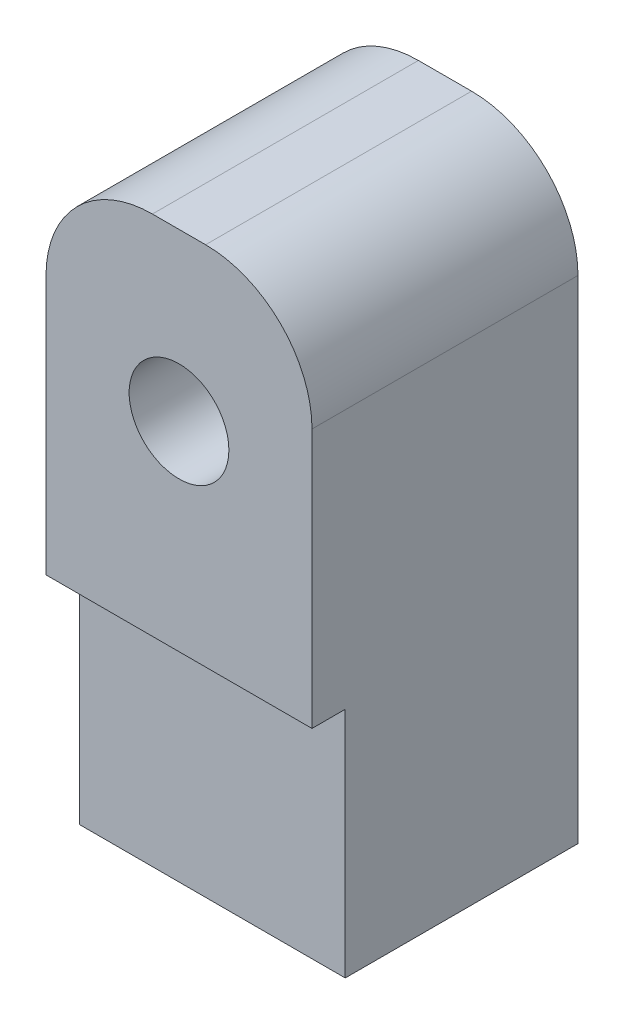
SolidWorks part; units mm, degrees
material "Plain Carbon Steel"
ref_plane "Front Plane" through (0, 0, 0) normal (0, 0, 1) x (1, 0, 0)
ref_plane "Top Plane" through (0, 0, 0) normal (0, 1, 0) x (1, 0, 0)
ref_plane "Right Plane" through (0, 0, 0) normal (1, 0, 0) x (0, 0, -1)
sketch "Sketch1" plane through (0, 0, 0) normal (0, 0, 1) x (1, 0, 0)
  line L0 (-12.7, 0) -> (12.7, 0)
  line L1 (12.7, 0) -> (12.7, 46.99)
  line L2 (2.54, 57.15) -> (-2.54, 57.15)
  line L3 (-12.7, 46.99) -> (-12.7, 0)
  line L4 (0, 0) -> (0, 50000) construction
  arc A0 (12.7, 46.99) -> (2.54, 57.15) centre (2.54, 46.99) ccw
  arc A1 (-2.54, 57.15) -> (-12.7, 46.99) centre (-2.54, 46.99) ccw
  circle A2 centre (0, 41.275) radius 4.7625
  dimension "D4" = 9.525
  dimension "D1" = 25.4
  dimension "D2" = 46.99
  dimension "D3" = 57.15
  dimension "D5" = 15.875
extrude "Boss-Extrude1" add sketch "Sketch1" against normal blind 25.4 contours A2 L4 | L4 A2 | L4 L0 L1 A0 L2 A2 | L0 L4 A2 L2 A1 L3 region at (-6.4455, 27.0253, 0) region at (6.4455, 27.0253, 0) region at (-2.0213, 41.275, 0) region at (2.0213, 41.275, 0)
extrude "Cut-Extrude1" cut sketch "Sketch1<3>" against normal blind 22.225 contours A2 L4 | L4 A2 region at (-2.0213, 41.275, 0) region at (2.0213, 41.275, 0)
sketch "Sketch1<3>" plane through (0, 0, 0) normal (0, 0, 1) x (1, 0, 0) same geometry as "Sketch1"
sketch "Sketch2" plane through (0, 0, -22.225) normal (0, 0, 1) x (1, 0, 0)
  circle A0 centre (0, 41.275) radius 6.0325
  dimension "D1" = 12.065
extrude "Cut-Extrude2" cut sketch "Sketch2" against normal through all
sketch "Sketch3" plane through (12.7, 0, 0) normal (1, 0, 0) x (0, 0, -1)
  line L1 (3.175, 0) -> (0, 0)
  line L2 (3.175, 0) -> (3.175, 22.225)
  line L3 (3.175, 22.225) -> (0, 22.225)
  line L4 (0, 0) -> (0, 22.225)
  dimension "D1" = 3.175
  dimension "D2" = 22.225
extrude "Cut-Extrude4" cut sketch "Sketch3" against normal through all
sketch "Sketch4" plane through (0, 0, 0) normal (0, -1, 0) x (1, 0, 0)
  line L1 (-12.7, 0) -> (12.7, 0) construction
  line L2 (-12.7, 0) -> (-12.7, -25.4) construction
  line L3 (-12.7, -25.4) -> (12.7, -25.4) construction
  line L4 (12.7, 0) -> (12.7, -25.4) construction
  circle A0 centre (0, -12.7) radius 6.35
  point P9 (12.7, -12.7)
  dimension "D1" = 12.7
extrude "Cut-Extrude5" cut sketch "Sketch4" against normal blind 30.1752
